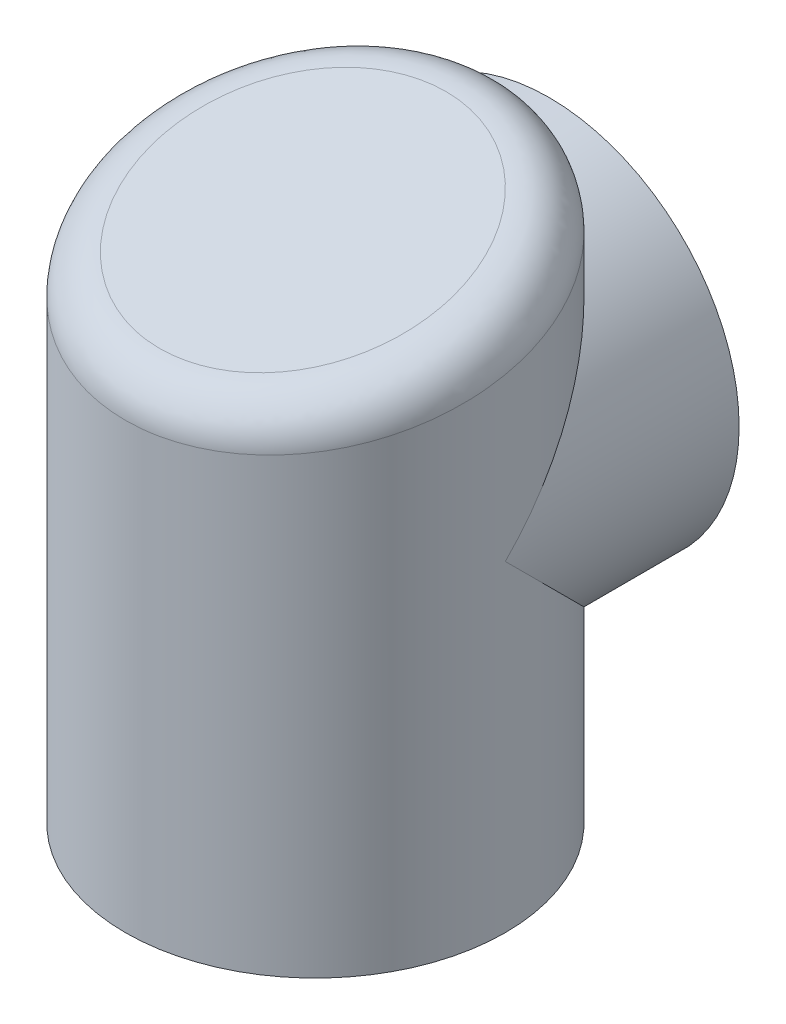
SolidWorks part; units mm, degrees
ref_plane "Front Plane" through (0, 0, 0) normal (0, 0, 1) x (1, 0, 0)
ref_plane "Top Plane" through (0, 0, 0) normal (0, 1, 0) x (1, 0, 0)
ref_plane "Right Plane" through (0, 0, 0) normal (1, 0, 0) x (0, 0, -1)
sketch "Sketch1" plane through (0, 0, 0) normal (0, 1, 0) x (1, 0, 0)
  circle A0 centre (0, 0) radius 32.5
  dimension "D1" = 65
extrude "Boss-Extrude1" add sketch "Sketch1" along normal blind 45 and the other way blind 55
sketch "Sketch2" plane through (0, 0, 0) normal (1, 0, 0) x (0, 0, -1)
  line L0 (32.5, 45) -> (-32.5, 45)
  line L1 (-32.5, 45) -> (-32.5, 27)
  line L2 (-32.5, 27) -> (32.5, 45)
  dimension "D1" = 18
extrude "Cut-Extrude1" cut sketch "Sketch2" against normal through all both and the other way through all
fillet "Fillet1" radius 8 1 edges at (0, 45, -32.5)
sketch "Sketch3" plane through (0, 0, 0) normal (0, 0, 1) x (1, 0, 0)
  circle A0 centre (0, 0) radius 32.5
  dimension "D1" = 65
extrude "Boss-Extrude2" add sketch "Sketch3" against normal blind 40
ref_plane "Plane1" through (0, 0, 0) normal (0, -1, 0) x (-1, 0, 0)
sketch "Sketch4" plane through (0, 0, 0) normal (0, -1, 0) x (-1, 0, 0)
  line L0 (-32.5, 0) -> (32.5, 0) construction
  line L2 (0, 32.5) -> (0, -32.5) construction
  circle A0 centre (0, 0) radius 32.5 construction
  circle A1 centre (0, 0) radius 32.5 construction
  arc A2 (32.5, 0) -> (-32.5, 0) centre (0, 0) ccw construction
  point P7 (0, 0)
